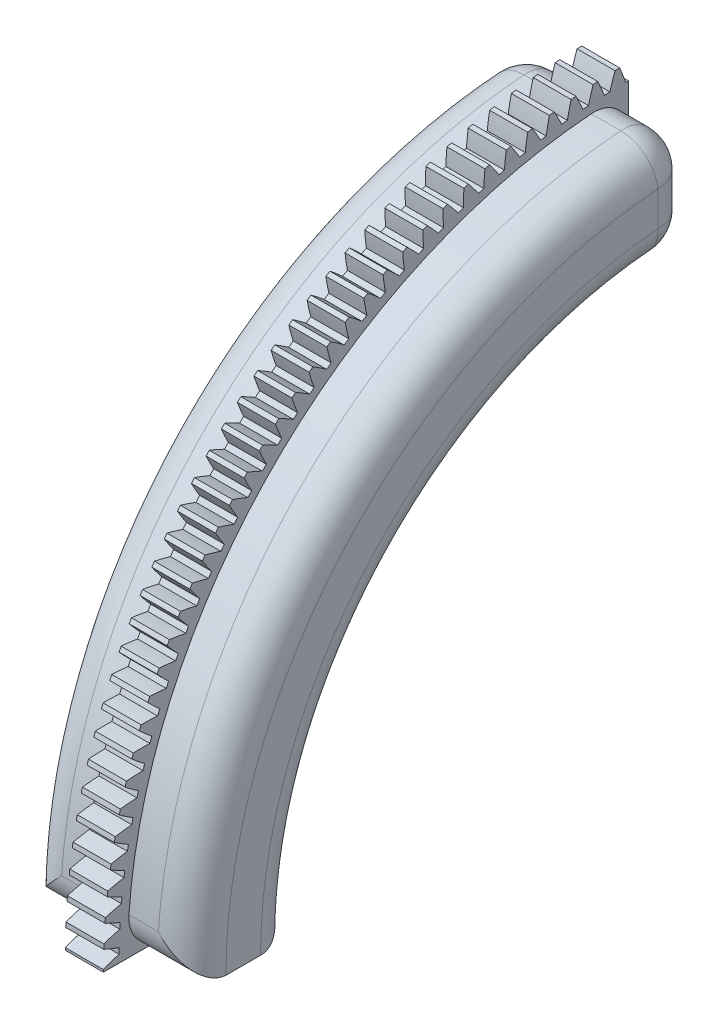
SolidWorks part; units mm, degrees
ref_plane "Plane1" through (0, 0, 0) normal (0, 0, 1) x (1, 0, 0)
ref_plane "Plane2" through (0, 0, 0) normal (0, 1, 0) x (1, 0, 0)
ref_plane "Plane3" through (0, 0, 0) normal (1, 0, 0) x (0, 0, -1)
other "Configuration Table"
sketch "HoldingSke" plane through (0, 0, 0) normal (0, 1, 0) x (1, 0, 0)
  line L0 (0, 0) -> (-0.866, -0.5)
  line L1 (-15, 0) -> (100, 0) construction
  line L2 (0, 0) -> (-2.1039, 2.3779)
  line L3 (0, 0) -> (-11.863, 4.5341)
  line L4 (0, 0) -> (-7.479, 4.318)
  line L5 (0, 0) -> (-46.8476, -17.4728)
  line L6 (0, 0) -> (-4.5593, -3.0762)
  line L7 (-2.1039, 2.3779) -> (8.6586, 51.2059)
  line L8 (-76.2, 54.61) -> (-75.2, 54.61)
  line L9 (-71.009, 38.7566) -> (-53.1078, 45.2721)
  line L10 (-76.2, 71.12) -> (104.1128, 71.12)
  line L11 (0, 0) -> (-5.5, 0)
  line L12 (-76.2, 101.6) -> (-76.162, 101.6)
  line L13 (24.9733, 27.94) -> (52.9518, 28.4284)
  line L14 (24.9733, 27.94) -> (24.9743, 27.94)
  line L15 (24.9733, 27.94) -> (100.4006, 29.5858)
  line L16 (-63.627, -1) -> (-12.827, -1)
  circle A0 centre (0, 0) radius 4
  circle A1 centre (0, 0) radius 37.5
  circle A2 centre (0, 0) radius 37.5
  circle A3 centre (0, 0) radius 4
  dimension "MHD" = 75
  dimension "Hub_dia" = 75
  dimension "Bore" = 8
  dimension "MBD" = 8
  dimension "Num_teeth" = 150
  dimension "Pitch" = 1
  dimension "Overall_len" = 50
  dimension "Show_teeth" = 150
  dimension "Thickness" = 5.5
  dimension "OAL" = 50.0001
  dimension "T_dim" = 1
  dimension "Ap" = 20
  dimension "H" = 19.05
  dimension "Pitch_radius" = 180.3128
  dimension "Width" = 5.5
  dimension "Backlash" = 0.038
  dimension "Addendum_fac" = 1
  dimension "Dedendum_fac" = 1.25
  dimension "Clearance_fac" = 0.25
  dimension "Dedendum_add" = 0.001
  dimension "Module" = 1
sketch "BasProSke" plane through (0, 0, 0) normal (0, 1, 0) x (1, 0, 0)
  line L0 (-10, 0) -> (60, 0) construction
  line L1 (0, 0) -> (0, 76)
  line L2 (0, 0) -> (5.5, 0)
  line L3 (5.5, 0) -> (5.5, 76)
  line L4 (5.5, 76) -> (0, 76)
  dimension "Thickness" = 5.5
  dimension "Diameter" = 152
revolve "Base-Revolve" add sketch "BasProSke" angle 360 about L0
sketch "TooCutSke" plane through (0, 0, 0) normal (1, 0, 0) x (0, 0, -1)
  line L1 (0, 0) -> (0, 107) construction
  line L2 (0, 0) -> (-0.8519, 74.9952) construction
  line L3 (0, 0) -> (-3.1412, 149.9602) construction
  line L4 (-0.8519, 74.9952) -> (-1.5706, 74.9801) construction
  arc A0 (0.4067, 73.7479) -> (-0.4067, 73.7479) centre (0, 0) ccw
  arc A1 (1.263, 76.0149) -> (-1.263, 76.0149) centre (0, 0) ccw
  circle A2 centre (0, 0) radius 75 construction
  circle A3 centre (0, 0) radius 70.4769 construction
  arc A4 (-0.4067, 73.7479) -> (-1.263, 76.0149) centre (-28.8767, 64.2895) ccw
  arc A5 (1.263, 76.0149) -> (0.4067, 73.7479) centre (28.8767, 64.2895) ccw
  dimension "Root_dia" = 147.498
  dimension "Overcut_dia" = 152.0508
  dimension "Pitch_dia" = 150
  dimension "Base_dia" = 140.9539
  dimension "Flank_rad" = 30
  dimension "Half_ang" = 1.2
  dimension "Half_CT" = 0.7189
extrude "ToothCut" cut sketch "TooCutSke" along normal through all
fillet "Breaks" [suppressed] radius 0.02 tangent propagation no
fillet "RootFillets" [suppressed] radius 0.251
pattern_circular "TeethCuts" count 150 every 2.4 about axis through (-10, 0, 0) along (1, 0, 0) of "ToothCut", "RootFillets", "Breaks"
sketch "HubNeaOneSke" plane through (0, 0, 0) normal (-1, 0, 0) x (0, 0, 1)
  circle A0 centre (0, 0) radius 37.5
  dimension "Diameter" = 75
extrude "HubNearOne" [suppressed] add sketch "HubNeaOneSke" along normal blind 44.5001
sketch "HubNeaBotSke" plane through (0, 0, 0) normal (-1, 0, 0) x (0, 0, 1)
  circle A0 centre (0, 0) radius 37.5
  dimension "Diameter" = 75
extrude "HubNearBoth" [suppressed] add sketch "HubNeaBotSke" along normal blind 22.25
ref_plane "FarPln" through (5.5, 0, 0) normal (1, 0, 0) x (0, 0, -1)
sketch "HubFarSke" plane through (5.5, 0, 0) normal (1, 0, 0) x (0, 0, -1)
  circle A0 centre (0, 0) radius 37.5
  dimension "Diameter" = 75
extrude "HubFar" [suppressed] add sketch "HubFarSke" along normal blind 22.25
sketch "BorSke" plane through (0, 0, 0) normal (1, 0, 0) x (0, 0, -1)
  circle A0 centre (0, 0) radius 4
  dimension "Diameter" = 8
extrude "Bore" cut sketch "BorSke" along normal mid plane 100.0001
sketch "KeySke" plane through (0, 0, 0) normal (1, 0, 0) x (0, 0, -1)
  line L0 (-1, 0) -> (-1, 5)
  line L1 (-1, 5) -> (1, 5)
  line L2 (1, 5) -> (1, 0)
  line L3 (0, 0) -> (0, 34) construction
  line L4 (-1, 0) -> (1, 0)
  dimension "Offset" = 5
  dimension "Width" = 2
extrude "Keyway" [suppressed] cut sketch "KeySke" along normal mid plane 100.0001
pattern_circular "Keyway2" [suppressed] count 2 every 90 about axis through (-10, 0, 0) along (1, 0, 0) reverse direction yes
sketch "ｽｹｯﾁ1" plane through (5.5, 0, 0) normal (1, 0, 0) x (0, 0, -1)
  line L0 (0, 100) -> (0, 72.5)
  line L1 (-72.5, 0) -> (-100, 0)
  arc A0 (-100, 0) -> (0, 100) centre (0, 0) ccw
  arc A1 (0, 72.5) -> (-72.5, 0) centre (0, 0) ccw
  dimension "D1" = 200
  dimension "D2" = 145
extrude "ｶｯﾄ - 押し出し1" cut sketch "ｽｹｯﾁ1" against normal through all
ref_plane "平面1" through (5.5, 0, 72.5) normal (0, -1, 0) x (-1, 0, 0)
ref_plane "平面2" through (2.75, 0, 0) normal (1, 0, 0) x (0, 0, -1)
sketch "ｽｹｯﾁ2" plane through (2.75, 0, 0) normal (1, 0, 0) x (0, 0, -1)
  line L0 (0, 72.5) -> (0, 57.5)
  line L1 (-57.5, 0) -> (-72.5, 0)
  arc A0 (0, 72.5) -> (-72.5, 0) centre (0, 0) ccw construction
  arc A1 (0, 72.5) -> (-72.5, 0) centre (0, 0) ccw
  arc A2 (0, 57.5) -> (-57.5, 0) centre (0, 0) ccw
  dimension "D1" = 115
extrude "ﾎﾞｽ - 押し出し1" add sketch "ｽｹｯﾁ2" along normal blind 12 and the other way blind 12
fillet "ﾌｨﾚｯﾄ1" radius 5 12 edges at (2.75, 57.5, 0) (-9.25, 65, 0) (14.75, 65, 0) (14.75, 51.2652, 51.2652) (14.75, 40.6586, 40.6586) (-9.25, 40.6586, 40.6586) (-9.25, 51.2652, 51.2652) (2.75, 0, 57.5) (10.125, 0, 72.5) (-4.625, 0, 72.5) (10.125, 72.5, 0) (-4.625, 72.5, 0)
equation "' \"Module@HoldingSke\" = 6.35"
equation "' \"Num_teeth@HoldingSke\" = 12"
equation "' \"Ap@HoldingSke\" =  20"
equation "' \"Ap@HoldingSke\" = 20"
equation "' \"Width@HoldingSke\" = 0.5 * 25.4"
equation "' \"Hub_dia@HoldingSke\"= 1 * 25.4"
equation "' \"Hub_dia@HoldingSke\" = 1 * 25.4"
equation "' \"Overall_len@HoldingSke\" = 1.0 * 25.4"
equation "' \"Bore@HoldingSke\" = 0.75 * 25.4"
equation "' \"T_dim@HoldingSke\" = 0.1 * 25.4"
equation "' \"Width@KeySke\" = 0.25 * 25.4"
equation "' \"Show_teeth@HoldingSke\" = 13"
equation "' \"Backlash@HoldingSke\" = 0.009 * 25.4"
equation "' \"Addendum_fac@HoldingSke\" = 1.0"
equation "' \"Dedendum_fac@HoldingSke\" = 1.25"
equation "' \"Dedendum_add@HoldingSke\" = 0.00005 * 25.4"
equation "' \"Clearance_fac@HoldingSke\" = 0.25"
equation "\"Pitch@HoldingSke\" = 1 / \"Module@HoldingSke\""
equation "\"Overcut_dia@TooCutSke\" = (\"Num_teeth@HoldingSke\" + 2 * \"Addendum_fac@HoldingSke\") / \"Pitch@HoldingSke\" + 0.002 * 25.4"
equation "\"Pitch_dia@TooCutSke\" = \"Num_teeth@HoldingSke\" / \"Pitch@HoldingSke\""
equation "\"Base_dia@TooCutSke\" = \"Num_teeth@HoldingSke\" / \"Pitch@HoldingSke\" * cos((\"Ap@HoldingSke\"  * 3.14159265 / 180))"
equation "\"Root_dia@TooCutSke\" = (\"Num_teeth@HoldingSke\" + 2) / \"Pitch@HoldingSke\" - 2 * (\"Addendum_fac@HoldingSke\" + \"Dedendum_fac@HoldingSke\") / \"Pitch@HoldingSke\" - \"Dedendum_add@HoldingSke\" * 2"
equation "\"Half_ang@TooCutSke\" = 180 / \"Num_teeth@HoldingSke\""
equation "\"Half_CT@TooCutSke\" = \"Num_teeth@HoldingSke\" / \"Pitch@HoldingSke\" * sin((3.14159265 / 2 / \"Num_teeth@HoldingSke\")) / 2 - 7 * \"Backlash@HoldingSke\" / 4"
equation "\"Flank_rad@TooCutSke\" = \"Num_teeth@HoldingSke\" / \"Pitch@HoldingSke\" / 5"
equation "\"Radius@RootFillets\" = \"Clearance_fac@HoldingSke\" / \"Pitch@HoldingSke\" + \"Dedendum_add@HoldingSke\""
equation "\"Break_rad@Breaks\" = 0.02 / \"Pitch@HoldingSke\""
equation "\"Thickness@HoldingSke\" = \"Width@HoldingSke\""
equation "\"OAL@HoldingSke\" = \"Thickness@HoldingSke\""
equation "\"MHD@HoldingSke\" = (\"Num_teeth@HoldingSke\" + 2) / \"Pitch@HoldingSke\" - 2 * (\"Addendum_fac@HoldingSke\" + \"Dedendum_fac@HoldingSke\")  / \"Pitch@HoldingSke\" - \"Dedendum_add@HoldingSke\" * 2"
equation "\"MBD@HoldingSke\" = (\"Num_teeth@HoldingSke\" + 2) / \"Pitch@HoldingSke\" - 2 * (\"Addendum_fac@HoldingSke\" + \"Dedendum_fac@HoldingSke\")  / \"Pitch@HoldingSke\" - \"Dedendum_add@HoldingSke\" * 2 - 0.002 * 25.4"
equation "\"MHD@HoldingSke\" = ((sgn( \"MHD@HoldingSke\" - \"Hub_dia@HoldingSke\" )-1)*( \"MHD@HoldingSke\" - \"Hub_dia@HoldingSke\" ))/-2+ \"Hub_dia@HoldingSke\""
equation "\"MBD@HoldingSke\" = ((sgn( \"MBD@HoldingSke\" - \"Bore@HoldingSke\" )-1)*( \"MBD@HoldingSke\" - \"Bore@HoldingSke\" ))/-2+ \"Bore@HoldingSke\""
equation "\"OAL@HoldingSke\" = ((sgn( \"OAL@HoldingSke\" - \"Overall_len@HoldingSke\" )+1)*( \"OAL@HoldingSke\" - \"Overall_len@HoldingSke\" ))/2 + \"Overall_len@HoldingSke\" + 0.000002 * 25.4"
equation "\"Num_teeth@TeethCuts\" = int( \"Show_teeth@HoldingSke\" ) + 1"
equation "\"Num_teeth@TeethCuts\" = ((sgn( \"Num_teeth@TeethCuts\" - \"Num_teeth@HoldingSke\" )-1)*( \"Num_teeth@TeethCuts\" - \"Num_teeth@HoldingSke\" ))/-2+ \"Num_teeth@HoldingSke\""
equation "\"Num_teeth@TeethCuts\" = ((sgn( \"Num_teeth@TeethCuts\" - 2.0)+1)*( \"Num_teeth@TeethCuts\" - 2.0))/2 +2.0"
equation "\"Angle@TeethCuts\" = 360.0 / \"Num_teeth@HoldingSke\""
equation "\"Diameter@BasProSke\" = (\"Num_teeth@HoldingSke\" + 2 * \"Addendum_fac@HoldingSke\") / \"Pitch@HoldingSke\""
equation "\"Thickness@BasProSke\"  = \"Thickness@HoldingSke\""
equation "' \"Fillet_rad@BasProSke\" =  \"Thickness@HoldingSke\" * 0.05"
equation "' \"Fillet_rad@BasProSke\" = \"Thickness@HoldingSke\" * 0.05"
equation "\"MHD@HoldingSke\" = ((sgn( \"MHD@HoldingSke\" - \"Root_dia@TooCutSke\" )-1)*( \"MHD@HoldingSke\" - \"Root_dia@TooCutSke\" ))/-2+ \"Root_dia@TooCutSke\""
equation "\"Diameter@HubNeaOneSke\" = \"MHD@HoldingSke\""
equation "\"Length@HubNearOne\" = \"OAL@HoldingSke\" - \"Thickness@BasProSke\""
equation "\"Diameter@HubNeaBotSke\" = \"MHD@HoldingSke\""
equation "\"Length@HubNearBoth\" = ( \"OAL@HoldingSke\" - \"Thickness@BasProSke\" ) / 2.0"
equation "\"Thickness@FarPln\" = \"Thickness@BasProSke\""
equation "\"Diameter@HubFarSke\" = \"MHD@HoldingSke\""
equation "\"Length@HubFar\" = ( \"OAL@HoldingSke\" - \"Thickness@BasProSke\" ) / 2.0"
equation "\"Diameter@BorSke\" = \"MBD@HoldingSke\""
equation "\"D1@Bore\" = \"OAL@HoldingSke\" * 2.0"
equation "\"D1@Keyway\" = \"OAL@HoldingSke\" * 2.0"
equation "\"Offset@KeySke\" = \"T_dim@HoldingSke\" + \"MBD@HoldingSke\" / 2.0"
